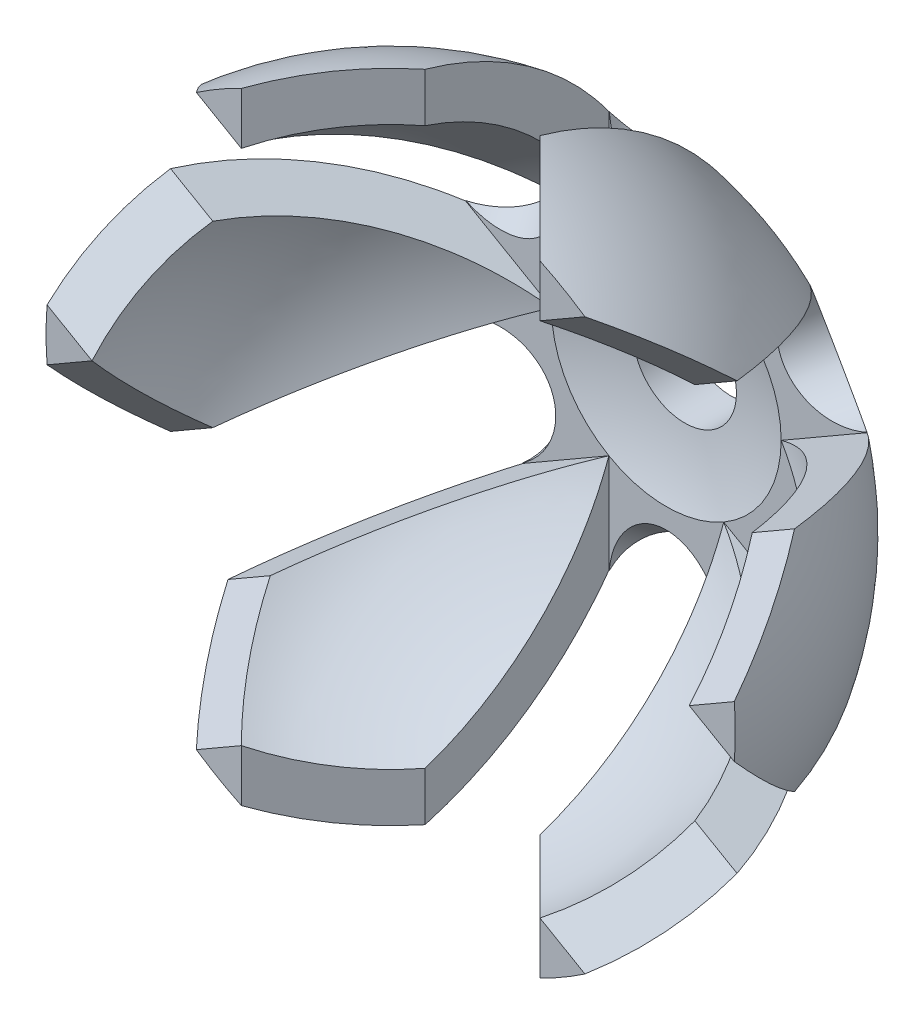
SolidWorks part; units mm, degrees
ref_plane "Front Plane" through (0, 0, 0) normal (0, 0, 1) x (1, 0, 0)
ref_plane "Top Plane" through (0, 0, 0) normal (0, 1, 0) x (1, 0, 0)
ref_plane "Right Plane" through (0, 0, 0) normal (1, 0, 0) x (0, 0, -1)
sketch "Sketch1" plane through (0, 0, 0) normal (0, 1, 0) x (1, 0, 0)
  line L0 (0, 15) -> (0, 13)
  line L1 (15, 0) -> (13, 0)
  line L2 (0, 0) -> (15, 0) construction
  line L3 (0, 0) -> (0, 15) construction
  arc A0 (0, 13) -> (13, 0) centre (0, 0) cw
  arc A1 (0, 15) -> (15, 0) centre (0, 0) cw
  point P6 (0, 0)
  dimension "D1" = 13
  dimension "D2" = 15
revolve "Revolve1" add sketch "Sketch1" angle 360 about L0
sketch "Sketch2" plane through (0, 0, 0) normal (0, 0, 1) x (1, 0, 0)
  circle A0 centre (0, 0) radius 2.25
  dimension "D1" = 4.5
extrude "Cut-Extrude1" cut sketch "Sketch2" against normal through all both and the other way through all
sketch "Sketch3" plane through (0, 0, 0) normal (0, 1, 0) x (1, 0, 0)
  line L0 (-2.5, 0) -> (-2.5, 12)
  line L1 (-15, 0) -> (15, 0) construction
  line L2 (2.5, 0) -> (2.5, 12)
  line L3 (-2.5, 12) -> (2.5, 12)
  point P6 (0, 12)
  dimension "D1" = 5
  dimension "D2" = 12
extrude "Cut-Extrude2" cut sketch "Sketch3" against normal through all both and the other way through all
sketch "Sketch4" plane through (0, 0, -12) normal (0, 0, 1) x (1, 0, 0)
  arc A0 (2.5, 8.6458) -> (-2.5, 8.6458) centre (0, 0) ccw construction
  point P0 (0, 9)
ref_plane "Plane1" through (0, 9, -12) normal (0, 0.6, -0.8) x (-1, 0, 0)
sketch "Sketch5" plane through (0, 9, -12) normal (0, 0.6, -0.8) x (-1, 0, 0)
  line L0 (2.5, 11.8322) -> (2.5, -0.2834) construction
  line L1 (-2.5, -0.2834) -> (-2.5, 11.8322) construction
  line L2 (-2.5, 0) -> (2.5, 0)
  arc A0 (2.5, 0) -> (-2.5, 0) centre (0, 0) cw
extrude "Cut-Extrude3" cut sketch "Sketch5" against normal through all both and the other way through all
pattern_circular "CirPattern1" count 6 over 360 about axis through (0, 0, -15) along (0, 0, 1) of "Cut-Extrude2", "Cut-Extrude3" reverse direction yes
chamfer "Chamfer1" distance 4 angle 45 12 edges at (-2.5, -13.7738, 0) (2.5, -13.7738, 0) (2.5, 13.7738, 0) (-2.5, 13.7738, 0) (13.1784, -4.7218, 0) (-10.6784, 9.052, 0) (-13.1784, 4.7218, 0) (10.6784, -9.052, 0) (10.6784, 9.052, 0) (-13.1784, -4.7218, 0) (-10.6784, -9.052, 0) (13.1784, 4.7218, 0)
